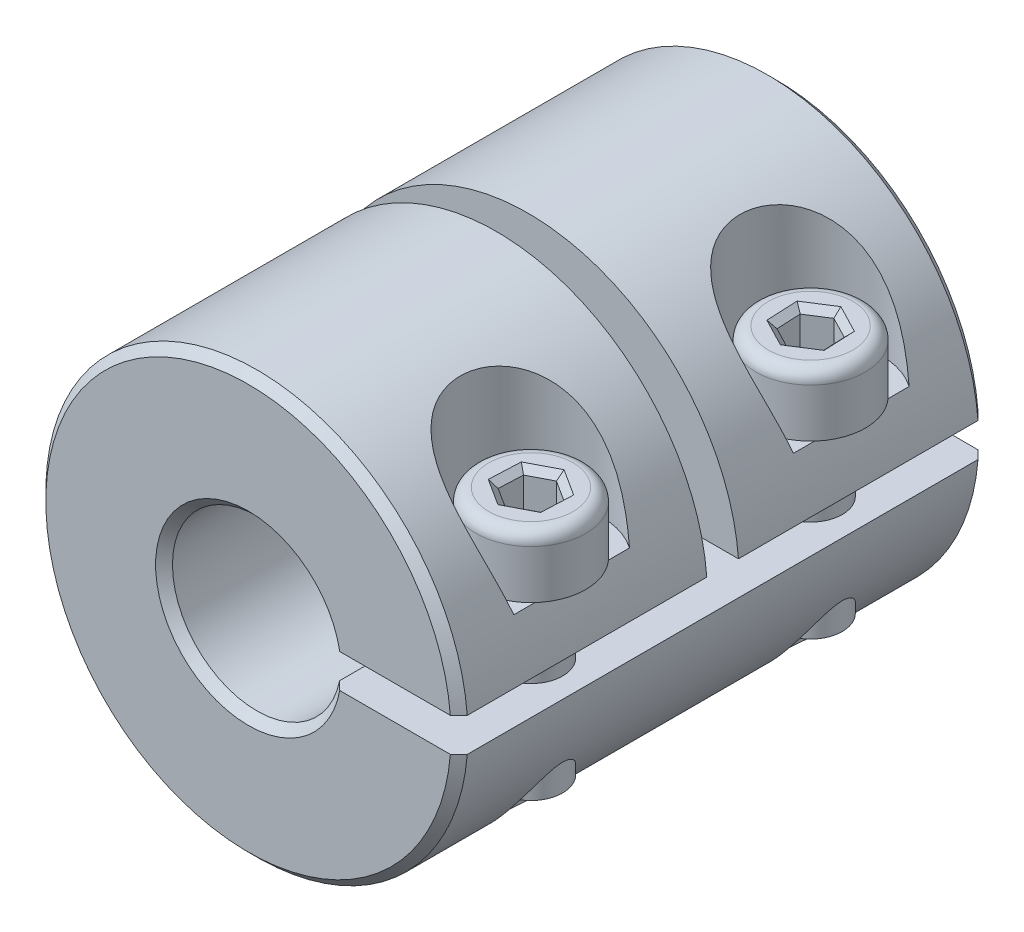
SolidWorks part; units mm, degrees
ref_plane "Спереди" through (0, 0, 0) normal (0, 0, 1) x (1, 0, 0)
ref_plane "Сверху" through (0, 0, 0) normal (0, 1, 0) x (1, 0, 0)
ref_plane "Справа" through (0, 0, 0) normal (1, 0, 0) x (0, 0, -1)
sketch "Эскиз1" plane through (0, 0, 0) normal (0, 0, 1) x (1, 0, 0)
  line L0 (0, 0) -> (13.6644, 0) construction
  line L1 (0, -0.8) -> (13.6644, -0.8)
  line L2 (0, 0.8) -> (13.6644, 0.8)
  circle A0 centre (0, 0) radius 10
  circle A1 centre (0, 0) radius 2.5
  circle A2 centre (0, 0) radius 4
  dimension "D1" = 5
  dimension "D2" = 8
  dimension "D3" = 20
  dimension "D4" = 0.8
  dimension "D5" = 0.8
extrude "Бобышка-Вытянуть1" add sketch "Эскиз1" along normal blind 25 contours A2 L2 A0 L1 region at (6.9436, -1.0826, 0)
extrude "Бобышка-Вытянуть2" add sketch "Эскиз1<3>" along normal blind 7 contours L2 A2 L1 A1 region at (3.1439, -0.9126, 0)
sketch "Эскиз1<3>" plane through (0, 0, 0) normal (0, 0, 1) x (1, 0, 0) same geometry as "Эскиз1"
sketch "Эскиз2" plane through (0, 0, 0) normal (1, 0, 0) x (0, 0, -1)
  line L0 (-25, -0.8) -> (0, -0.8) construction
  line L1 (-13.25, -0.8) -> (-11.75, -0.8)
  line L2 (-13.25, -0.8) -> (-13.25, 13.6592)
  line L3 (-13.25, 13.6592) -> (-11.75, 13.6592)
  line L4 (-11.75, -0.8) -> (-11.75, 13.6592)
  line L5 (0, -10) -> (0, 10) construction
  line L6 (-25, 10) -> (-25, -10) construction
  dimension "D1" = 11.75
  dimension "D2" = 11.75
extrude "Вырез-Вытянуть1" cut sketch "Эскиз2" against normal through all and the other way through all
sketch "Эскиз3" plane through (0, 0, 0) normal (0, 1, 0) x (1, 0, 0)
  line L0 (9.9679, -12.5) -> (15.4622, -12.5) construction
  line L1 (9.9679, -25) -> (9.9679, 0) construction
  line L2 (2.3685, 0) -> (9.9679, 0) construction
  circle A0 centre (7.5122, -5.875) radius 3.35
  circle A1 centre (7.5122, -5.875) radius 1.5
  circle A2 centre (7.5122, -19.125) radius 1.5
  circle A3 centre (7.5122, -19.125) radius 3.35
  dimension "D1" = 6.7
  dimension "D2" = 3
  dimension "D3" = 5.875
extrude "Вырез-Вытянуть2" cut sketch "Эскиз3" against normal through all and the other way through all contours A2 | A1 region at (7.5122, 0, 5.875) region at (7.5122, 0, 19.125)
extrude "Вырез-Вытянуть3" cut sketch "Эскиз3<3>" along normal through all from offset 3.3 contours A3 A2 | A0 A1 region at (4.2569, 0, 5.875) region at (4.2569, 0, 19.125)
sketch "Эскиз3<3>" plane through (0, 0, 0) normal (0, 1, 0) x (1, 0, 0) same geometry as "Эскиз3"
chamfer "Фаска1" distance 0.4 angle 45 4 edges at (-2.5, 0, 0) (-10, 0, 0) (-4, 0, 25) (-10, 0, 25)
sketch "Эскиз4" plane through (0, 3.3, 0) normal (0, 1, 0) x (1, 0, 0)
  circle A0 centre (7.5122, -5.875) radius 2.6
  circle A1 centre (7.5122, -5.875) radius 1.5
  dimension "D1" = 3
  dimension "D2" = 5.2
extrude "Бобышка-Вытянуть3" add sketch "Эскиз4" along normal blind 2.9 separate body contours A0
extrude "Бобышка-Вытянуть4" add sketch "Эскиз4<3>" against normal blind 8.9 contours A1
sketch "Эскиз4<3>" plane through (0, 3.3, 0) normal (0, 1, 0) x (1, 0, 0) same geometry as "Эскиз4"
sketch "Эскиз5" plane through (0, 6.2, 0) normal (0, 1, 0) x (1, 0, 0)
  line L1 (8.4854, -5.2536) -> (7.4607, -4.7214)
  line L2 (7.4607, -4.7214) -> (6.4874, -5.3428)
  line L3 (6.4874, -5.3428) -> (6.5389, -6.4964)
  line L4 (6.5389, -6.4964) -> (7.5637, -7.0286)
  line L5 (7.5637, -7.0286) -> (8.5369, -6.4072)
  line L6 (8.5369, -6.4072) -> (8.4854, -5.2536)
  circle A0 centre (7.5122, -5.875) radius 1 construction
  dimension "D1" = 2
extrude "Вырез-Вытянуть4" cut sketch "Эскиз5" against normal blind 2
fillet "Скругление1" radius 0.6 1 edges at (7.5122, 6.2, 8.475)
chamfer "Фаска2" distance 0.3 angle 45 12 edges at (7.9731, 6.2, 4.9875) (6.9741, 6.2, 5.0321) (6.5132, 6.2, 5.9196) (7.0513, 6.2, 6.7625) (8.0503, 6.2, 6.7179) (8.5112, 6.2, 5.8304) (8.0503, 4.2, 6.7179) (7.0513, 4.2, 6.7625) (6.5132, 4.2, 5.9196) (6.9741, 4.2, 5.0321) (7.9731, 4.2, 4.9875) (8.5112, 4.2, 5.8304)
ref_plane "Плоскость1" through (0, 0, 12.5) normal (0, 0, 1) x (1, 0, 0)
mirror "Зеркальное отражение1" about plane through (0, 0, 12.5) normal (0, 0, 1) of bodies 110
